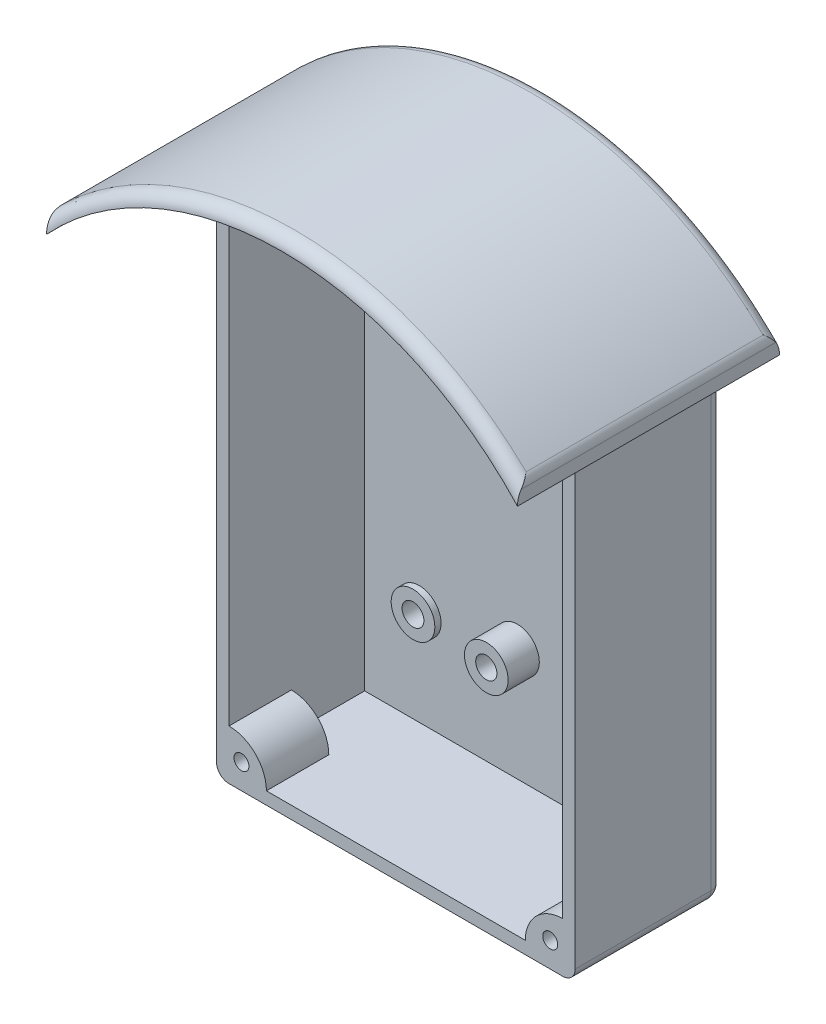
SolidWorks part; units mm, degrees
ref_plane "Piano frontale" through (0, 0, 0) normal (0, 0, 1) x (1, 0, 0)
ref_plane "Piano superiore" through (0, 0, 0) normal (0, 1, 0) x (1, 0, 0)
ref_plane "Piano destro" through (0, 0, 0) normal (1, 0, 0) x (0, 0, -1)
sketch "Schizzo1" plane through (0, 0, 0) normal (0, 0, 1) x (1, 0, 0)
  line L1 (-28.75, -45) -> (28.75, -45)
  line L2 (-28.75, -45) -> (-28.75, 45)
  line L4 (28.75, -45) -> (28.75, 45)
  line L5 (-28.75, -45) -> (28.75, 45) construction
  line L6 (-28.75, 45) -> (28.75, -45) construction
  line L7 (-18, -27.5) -> (18, -27.5) construction
  line L8 (-18, -27.5) -> (-18, 27.5) construction
  line L9 (-18, 27.5) -> (18, 27.5) construction
  line L10 (18, -27.5) -> (18, 27.5) construction
  line L11 (-18, -27.5) -> (18, 27.5) construction
  line L12 (-18, 27.5) -> (18, -27.5) construction
  circle A0 centre (-18, 27.5) radius 1.75
  circle A1 centre (18, 27.5) radius 1.75
  circle A2 centre (-18, -27.5) radius 1.75
  circle A3 centre (18, -27.5) radius 1.75
  arc A10 (28.75, 45) -> (-28.75, 45) centre (0, 0) ccw
  circle A11 centre (0, 15) radius 4
  point P0 (0, 0)
  point P6 (0, 0)
  dimension "D5" = 3.5
  dimension "D6" = 8
  dimension "D7" = 60
  dimension "D1" = 90
  dimension "D2" = 57.5
  dimension "D3" = 36
  dimension "D4" = 55
extrude "Estrusione-Estrusione1" add sketch "Schizzo1" along normal blind 2
sketch "Schizzo2" plane through (0, 0, 2) normal (0, 0, 1) x (1, 0, 0)
  circle A0 centre (-18, 27.5) radius 3.5
  circle A1 centre (18, 27.5) radius 3.5
  circle A2 centre (-18, -27.5) radius 3.5
  circle A3 centre (18, -27.5) radius 3.5
  circle A4 centre (-18, 27.5) radius 1.75
  circle A5 centre (18, 27.5) radius 1.75
  circle A6 centre (18, -27.5) radius 1.75
  circle A7 centre (-18, -27.5) radius 1.75
  dimension "D1" = 7
  dimension "D2" = 3.5
extrude "Estrusione-Estrusione2" add sketch "Schizzo2" along normal blind 1
sketch "Schizzo3" plane through (0, 0, 2) normal (0, 0, 1) x (1, 0, 0)
  line L3 (-28.75, 45) -> (-28.75, -45) construction
  circle A0 centre (-2.25, -25) radius 1.7
  circle A1 centre (-18, 37) radius 1.7
  circle A2 centre (18, 37) radius 1.7
  circle A3 centre (-2.25, -25) radius 3.5
  circle A4 centre (-18, 37) radius 3.5
  circle A5 centre (18, 37) radius 3.5
  dimension "D1" = 3.4
  dimension "D2" = 7
  dimension "D3" = 8
  dimension "D4" = 36
  dimension "D5" = 10.75
  dimension "D6" = 62
  dimension "D7" = 26.5
sketch "Schizzo6" plane through (0, 0, 2) normal (0, 0, 1) x (1, 0, 0)
  line L0 (-28.75, 42.6075) -> (-28.75, -45)
  line L1 (-28.75, 45) -> (-28.75, -45) construction
  line L2 (-28.75, -45) -> (28.75, -45)
  line L3 (28.75, -45) -> (28.75, 42.6075)
  line L10 (26.75, 43.8908) -> (26.75, -43)
  line L11 (26.75, -43) -> (-26.75, -43)
  line L13 (37.75, 37.769) -> (37.75, 34.8841)
  line L14 (-37.75, 34.8841) -> (-37.75, 37.769)
  line L15 (-26.75, -43) -> (-26.75, 43.8908)
  arc A0 (-37.75, 37.769) -> (37.75, 37.769) centre (0, 0) cw
  arc A4 (28.75, 45) -> (-28.75, 45) centre (0, 0) ccw construction
  arc A5 (-37.75, 34.8841) -> (37.75, 34.8841) centre (0, 0) cw
  point P5 (0, 0)
  arc M18 (28.75, 45) -> (-28.75, 45) centre (0, 0) ccw
  line M19 (-28.75, 45) -> (-28.75, -45)
  line M20 (-28.75, -45) -> (28.75, -45)
  line M21 (28.75, -45) -> (28.75, 45)
  dimension "D4" = 2
  dimension "D5" = 9
  dimension "D1" = 2
  dimension "D2" = 2
  dimension "D3" = 2
extrude "Estrusione-Estrusione5" add sketch "Schizzo6" along normal blind 21.75 contours A5 L10 L11 L15 M19 M20 M21 region at (-27.1857, 42.3697, 2)
extrude "Estrusione-Estrusione6" add sketch "Schizzo6<3>" along normal blind 40 and the other way blind 2 contours A5 L13 A0 M21 | A5 M19 M21 M18 | L14 A5 A0 M19 region at (-28.165, 43.8038, 2) region at (-33.3895, 40.2338, 2) region at (33.3895, 40.2338, 2)
sketch "Schizzo6<3>" plane through (0, 0, 2) normal (0, 0, 1) x (1, 0, 0) same geometry as "Schizzo6"
fillet "Raccordo2" radius 2 4 edges at (0, 53.4, 0) (-37.75, 37.769, 21) (0, 53.4, 42) (37.75, 37.769, 21) type face fillet first side face at (0, 45.5845, 21) second side face at (0, 19.5841, 0) second side face at (-37.75, 36.3266, 21) second side face at (37.75, 36.3266, 21) second side face at (0, 44.3633, 42)
fillet "Raccordo4" radius 2 2 edges at (-28.75, -1.1962, 0) (-28.75, -45, 11.875) type face fillet first side face at (-28.75, -1.1962, 11.875) second side face at (0, 1.0019, 0) second side face at (0, -45, 11.875)
fillet "Raccordo5" radius 2 2 edges at (1, -45, 0) (28.75, -1.1962, 0) type face fillet first side face at (1.047, 1.1589, 0) second side face at (28.75, -1.1962, 11.875) second side face at (1, -45, 11.875)
fillet "Raccordo6" radius 2 1 edges at (28.75, -45, 12.875) type face fillet first side face at (28.75, -1.1962, 12.875) second side face at (1, -45, 12.875)
sketch "Schizzo7" plane through (0, 0, 23.75) normal (0, 0, 1) x (1, 0, 0)
  line L0 (-26.75, -43) -> (-26.75, 43.8908) construction
  line L1 (26.75, 43.8908) -> (26.75, -43) construction
  line L2 (26.75, -43) -> (-26.75, -43) construction
  line L3 (-26.75, -43) -> (-26.75, 43.8908) construction
  line L4 (-26.75, -37) -> (-26.75, -43)
  line L5 (-26.75, -43) -> (-20.75, -43)
  line L6 (26.75, -37) -> (26.75, -43)
  line L7 (26.75, -43) -> (20.75, -43)
  line L9 (-26.75, 43.8908) -> (-26.75, 37.8908)
  line L10 (26.75, 37.8908) -> (26.75, 43.8908)
  line L12 (-28.75, 42.6075) -> (-28.75, -43) construction
  line L13 (28.75, -43) -> (28.75, 42.6075) construction
  line L14 (-26.75, -45) -> (26.75, -45) construction
  arc A0 (-21.453, 46.709) -> (-26.75, 37.8908) centre (-26.75, 43.8908) cw
  arc A1 (37.75, 34.8841) -> (-37.75, 34.8841) centre (0, 0) ccw construction
  arc A2 (21.453, 46.709) -> (26.75, 37.8908) centre (26.75, 43.8908) ccw
  arc A3 (26.75, 43.8908) -> (-26.75, 43.8908) centre (0, 0) ccw construction
  arc A4 (26.75, -37) -> (20.75, -43) centre (26.75, -43) ccw
  arc A5 (-26.75, -37) -> (-20.75, -43) centre (-26.75, -43) cw
  circle A6 centre (-24.75, 41.1075) radius 1.2
  circle A7 centre (24.75, 41.1075) radius 1.2
  circle A8 centre (24.75, -41) radius 1.2
  circle A9 centre (-24.75, -41) radius 1.2
  arc A10 (-26.75, 43.8908) -> (-21.453, 46.709) centre (0, 0) cw
  arc A11 (26.75, 43.8908) -> (21.453, 46.709) centre (0, 0) ccw
  line M21 (26.75, 43.8908) -> (26.75, -43)
  line M22 (26.75, -43) -> (-26.75, -43)
  line M23 (-26.75, -43) -> (-26.75, 43.8908)
  dimension "D1" = 6
  dimension "D5" = 2.4
  dimension "D2" = 4
  dimension "D3" = 1.5
  dimension "D4" = 4
  dimension "D6" = 4
extrude "Estrusione-Estrusione11" add sketch "Schizzo7" against normal blind 10 contours A10 A0 A6 M23 | A11 A2 A7 M21 | A5 A9 M23 M22 | A4 A8 M21 M22 region at (-22.5674, -38.8174, 23.75) region at (23.7808, 42.3569, 23.75) region at (22.5674, -38.8174, 23.75) region at (-23.7808, 42.3569, 23.75)
extrude "Estrusione-Estrusione12" add sketch "Schizzo3" along normal blind 5
